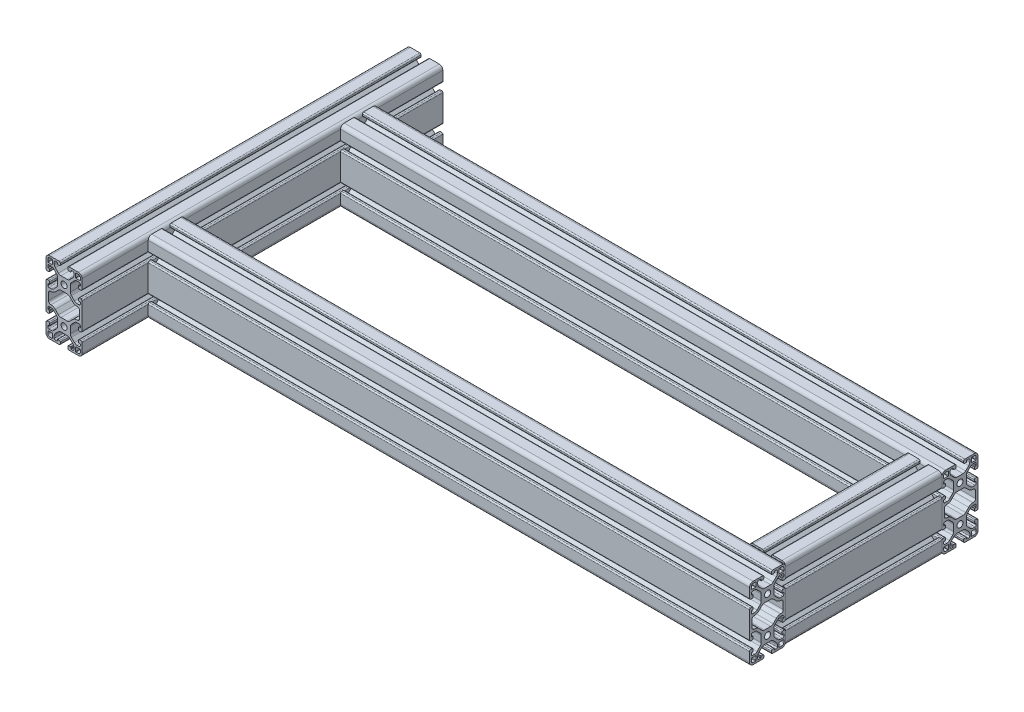
SolidWorks part; units mm, degrees
material "1060 Alloy"
material "1060 Alloy"
material "1060 Alloy"
material "1060 Alloy"
material "1060 Alloy"
ref_plane "Front Plane" through (0, 0, 0) normal (0, 0, 1) x (1, 0, 0)
ref_plane "Top Plane" through (0, 0, 0) normal (0, 1, 0) x (1, 0, 0)
ref_plane "Right Plane" through (0, 0, 0) normal (1, 0, 0) x (0, 0, -1)
sketch3d "3DSketch2"
  line L0 (250, 0, -80) -> (-250, 0, -80)
  line L1 (-265, 0, -150) -> (-265, 0, 150)
  line L2 (-250, 0, -80) -> (-265, 0, -80) construction
  line L3 (0, 0, 80) -> (0, 0, -80) construction
  line L4 (235, 0, -65) -> (235, 0, -80) construction
  line L6 (250, 0, 80) -> (-250, 0, 80)
  line L7 (0, 0, 0) -> (-265, 0, 0) construction
  line L8 (235, 0, 65) -> (235, 0, 80) construction
  line L9 (-250, 0, 80) -> (-265, 0, 80) construction
  line L10 (235, 0, 65) -> (235, 0, -65)
  point P4 (0, 0, 0)
  point P6 (-250, 0, -80)
  point P15 (0, 0, 0)
  point P18 (0, 0, 80)
  dimension "D1" = 15
  dimension "D5" = 160
  dimension "D2" = 300
  dimension "D3" = 15
  dimension "D4" = 500
other "Profile_6 60X30 L(1)" corner treatment butt1
ref_plane "Plane1" through (250, 0, -80) normal (1, 0, 0) x (0, 1, 0)
sketch "Sketch201" plane through (250, 0, -80) normal (1, 0, 0) x (0, 1, 0)
  line L0 (24.95, -13.5) -> (27, -13.5)
  line L1 (24.65, -9.95) -> (24.65, -13.2)
  line L2 (28.2, -9.65) -> (24.95, -9.65)
  line L3 (28.5, -12) -> (28.5, -9.95)
  line L4 (28.5, 9.95) -> (28.5, 12)
  line L5 (24.95, 9.65) -> (28.2, 9.65)
  line L6 (24.65, 13.2) -> (24.65, 9.95)
  line L7 (27, 13.5) -> (24.95, 13.5)
  line L8 (-24.95, 13.5) -> (-27, 13.5)
  line L9 (-24.65, 9.95) -> (-24.65, 13.2)
  line L10 (-28.2, 9.65) -> (-24.95, 9.65)
  line L11 (-28.5, 12) -> (-28.5, 9.95)
  line L12 (-28.5, -9.95) -> (-28.5, -12)
  line L13 (-24.95, -9.65) -> (-28.2, -9.65)
  line L14 (-24.65, -13.2) -> (-24.65, -9.95)
  line L15 (-27, -13.5) -> (-24.95, -13.5)
  line L16 (-4.85, -10.8069) -> (-4.85, -11)
  line L17 (-8.8713, -4.7145) -> (-6.3145, -7.2713)
  line L18 (-9.75, 2.5931) -> (-9.75, -2.5931)
  line L19 (-6.3145, 7.2713) -> (-8.8713, 4.7145)
  line L20 (-4.85, 11) -> (-4.85, 10.8069)
  line L21 (2.85, 13) -> (-2.85, 13)
  line L22 (4.85, 10.8069) -> (4.85, 11)
  line L23 (8.8713, 4.7145) -> (6.3145, 7.2713)
  line L24 (9.75, -2.5931) -> (9.75, 2.5931)
  line L25 (6.3145, -7.2713) -> (8.8713, -4.7145)
  line L26 (4.85, -11) -> (4.85, -10.8069)
  line L27 (-2.85, -13) -> (2.85, -13)
  line L28 (-10.9, -15) -> (10.9, -15)
  line L29 (-11.9, -12.8) -> (-11.9, -14)
  line L30 (-9.7, -12) -> (-11.1, -12)
  line L31 (-9.4, -13.2) -> (-9.4, -12.3)
  line L32 (-7.85, -13.5) -> (-9.1, -13.5)
  line L33 (-6.85, -10.8069) -> (-6.85, -12.5)
  line L34 (-10.2855, -6.1287) -> (-7.7287, -8.6855)
  line L35 (-17.5931, -5.25) -> (-12.4069, -5.25)
  line L36 (-22.2713, -8.6855) -> (-19.7145, -6.1287)
  line L37 (-23.15, -12.5) -> (-23.15, -10.8069)
  line L38 (-20.9, -13.5) -> (-22.15, -13.5)
  line L39 (-20.6, -12.3) -> (-20.6, -13.2)
  line L40 (-18.9, -12) -> (-20.3, -12)
  line L41 (-18.1, -14) -> (-18.1, -12.8)
  line L42 (-27, -15) -> (-19.1, -15)
  line L43 (-30, -4.1) -> (-30, -12)
  line L44 (-27.8, -3.1) -> (-29, -3.1)
  line L45 (-27, -5.3) -> (-27, -3.9)
  line L46 (-28.2, -5.6) -> (-27.3, -5.6)
  line L47 (-28.5, -7.15) -> (-28.5, -5.9)
  line L48 (-25.8069, -8.15) -> (-27.5, -8.15)
  line L49 (-21.1287, -4.7145) -> (-23.6855, -7.2713)
  line L50 (-20.25, 2.5931) -> (-20.25, -2.5931)
  line L51 (-23.6855, 7.2713) -> (-21.1287, 4.7145)
  line L52 (-27.5, 8.15) -> (-25.8069, 8.15)
  line L53 (-28.5, 5.9) -> (-28.5, 7.15)
  line L54 (-27.3, 5.6) -> (-28.2, 5.6)
  line L55 (-27, 3.9) -> (-27, 5.3)
  line L56 (-29, 3.1) -> (-27.8, 3.1)
  line L57 (-30, 12) -> (-30, 4.1)
  line L58 (-19.1, 15) -> (-27, 15)
  line L59 (-18.1, 12.8) -> (-18.1, 14)
  line L60 (-20.3, 12) -> (-18.9, 12)
  line L61 (-20.6, 13.2) -> (-20.6, 12.3)
  line L62 (-22.15, 13.5) -> (-20.9, 13.5)
  line L63 (-23.15, 10.8069) -> (-23.15, 12.5)
  line L64 (-19.7145, 6.1287) -> (-22.2713, 8.6855)
  line L65 (-12.4069, 5.25) -> (-17.5931, 5.25)
  line L66 (-7.7287, 8.6855) -> (-10.2855, 6.1287)
  line L67 (-6.85, 12.5) -> (-6.85, 10.8069)
  line L68 (-9.1, 13.5) -> (-7.85, 13.5)
  line L69 (-9.4, 12.3) -> (-9.4, 13.2)
  line L70 (-11.1, 12) -> (-9.7, 12)
  line L71 (-11.9, 14) -> (-11.9, 12.8)
  line L72 (10.9, 15) -> (-10.9, 15)
  line L73 (11.9, 12.8) -> (11.9, 14)
  line L74 (9.7, 12) -> (11.1, 12)
  line L75 (9.4, 13.2) -> (9.4, 12.3)
  line L76 (7.85, 13.5) -> (9.1, 13.5)
  line L77 (6.85, 10.8069) -> (6.85, 12.5)
  line L78 (10.2855, 6.1287) -> (7.7287, 8.6855)
  line L79 (17.5931, 5.25) -> (12.4069, 5.25)
  line L80 (22.2713, 8.6855) -> (19.7145, 6.1287)
  line L81 (23.15, 12.5) -> (23.15, 10.8069)
  line L82 (20.9, 13.5) -> (22.15, 13.5)
  line L83 (20.6, 12.3) -> (20.6, 13.2)
  line L84 (18.9, 12) -> (20.3, 12)
  line L85 (18.1, 14) -> (18.1, 12.8)
  line L86 (27, 15) -> (19.1, 15)
  line L87 (30, 4.1) -> (30, 12)
  line L88 (27.8, 3.1) -> (29, 3.1)
  line L89 (27, 5.3) -> (27, 3.9)
  line L90 (28.2, 5.6) -> (27.3, 5.6)
  line L91 (28.5, 7.15) -> (28.5, 5.9)
  line L92 (25.8069, 8.15) -> (27.5, 8.15)
  line L93 (21.1287, 4.7145) -> (23.6855, 7.2713)
  line L94 (20.25, -2.5931) -> (20.25, 2.5931)
  line L95 (23.6855, -7.2713) -> (21.1287, -4.7145)
  line L96 (27.5, -8.15) -> (25.8069, -8.15)
  line L97 (28.5, -5.9) -> (28.5, -7.15)
  line L98 (27.3, -5.6) -> (28.2, -5.6)
  line L99 (27, -3.9) -> (27, -5.3)
  line L100 (29, -3.1) -> (27.8, -3.1)
  line L101 (30, -12) -> (30, -4.1)
  line L102 (19.1, -15) -> (27, -15)
  line L103 (18.1, -12.8) -> (18.1, -14)
  line L104 (20.3, -12) -> (18.9, -12)
  line L105 (20.6, -13.2) -> (20.6, -12.3)
  line L106 (22.15, -13.5) -> (20.9, -13.5)
  line L107 (23.15, -10.8069) -> (23.15, -12.5)
  line L108 (19.7145, -6.1287) -> (22.2713, -8.6855)
  line L109 (12.4069, -5.25) -> (17.5931, -5.25)
  line L110 (7.7287, -8.6855) -> (10.2855, -6.1287)
  line L111 (6.85, -12.5) -> (6.85, -10.8069)
  line L112 (9.1, -13.5) -> (7.85, -13.5)
  line L113 (9.4, -12.3) -> (9.4, -13.2)
  line L114 (11.1, -12) -> (9.7, -12)
  line L115 (11.9, -14) -> (11.9, -12.8)
  circle A0 centre (-15, 0) radius 2.5
  circle A1 centre (15, 0) radius 2.5
  arc A2 (24.65, -13.2) -> (24.95, -13.5) centre (24.95, -13.2) ccw
  arc A3 (24.95, -9.65) -> (24.65, -9.95) centre (24.95, -9.95) ccw
  arc A4 (28.5, -9.95) -> (28.2, -9.65) centre (28.2, -9.95) ccw
  arc A5 (27, -13.5) -> (28.5, -12) centre (27, -12) ccw
  arc A6 (28.2, 9.65) -> (28.5, 9.95) centre (28.2, 9.95) ccw
  arc A7 (24.65, 9.95) -> (24.95, 9.65) centre (24.95, 9.95) ccw
  arc A8 (24.95, 13.5) -> (24.65, 13.2) centre (24.95, 13.2) ccw
  arc A9 (28.5, 12) -> (27, 13.5) centre (27, 12) ccw
  arc A10 (-24.65, 13.2) -> (-24.95, 13.5) centre (-24.95, 13.2) ccw
  arc A11 (-24.95, 9.65) -> (-24.65, 9.95) centre (-24.95, 9.95) ccw
  arc A12 (-28.5, 9.95) -> (-28.2, 9.65) centre (-28.2, 9.95) ccw
  arc A13 (-27, 13.5) -> (-28.5, 12) centre (-27, 12) ccw
  arc A14 (-28.2, -9.65) -> (-28.5, -9.95) centre (-28.2, -9.95) ccw
  arc A15 (-24.65, -9.95) -> (-24.95, -9.65) centre (-24.95, -9.95) ccw
  arc A16 (-24.95, -13.5) -> (-24.65, -13.2) centre (-24.95, -13.2) ccw
  arc A17 (-28.5, -12) -> (-27, -13.5) centre (-27, -12) ccw
  arc A18 (-4.85, -11) -> (-2.85, -13) centre (-2.85, -11) ccw
  arc A19 (-4.85, -10.8069) -> (-6.3145, -7.2713) centre (-9.85, -10.8069) ccw
  arc A20 (-9.75, -2.5931) -> (-8.8713, -4.7145) centre (-6.75, -2.5931) ccw
  arc A21 (-8.8713, 4.7145) -> (-9.75, 2.5931) centre (-6.75, 2.5931) ccw
  arc A22 (-6.3145, 7.2713) -> (-4.85, 10.8069) centre (-9.85, 10.8069) ccw
  arc A23 (-2.85, 13) -> (-4.85, 11) centre (-2.85, 11) ccw
  arc A24 (4.85, 11) -> (2.85, 13) centre (2.85, 11) ccw
  arc A25 (4.85, 10.8069) -> (6.3145, 7.2713) centre (9.85, 10.8069) ccw
  arc A26 (9.75, 2.5931) -> (8.8713, 4.7145) centre (6.75, 2.5931) ccw
  arc A27 (8.8713, -4.7145) -> (9.75, -2.5931) centre (6.75, -2.5931) ccw
  arc A28 (6.3145, -7.2713) -> (4.85, -10.8069) centre (9.85, -10.8069) ccw
  arc A29 (2.85, -13) -> (4.85, -11) centre (2.85, -11) ccw
  arc A30 (-11.9, -14) -> (-10.9, -15) centre (-10.9, -14) ccw
  arc A31 (-11.1, -12) -> (-11.9, -12.8) centre (-11.1, -12.8) ccw
  arc A32 (-9.4, -12.3) -> (-9.7, -12) centre (-9.7, -12.3) ccw
  arc A33 (-9.4, -13.2) -> (-9.1, -13.5) centre (-9.1, -13.2) ccw
  arc A34 (-7.85, -13.5) -> (-6.85, -12.5) centre (-7.85, -12.5) ccw
  arc A35 (-6.85, -10.8069) -> (-7.7287, -8.6855) centre (-9.85, -10.8069) ccw
  arc A36 (-10.2855, -6.1287) -> (-12.4069, -5.25) centre (-12.4069, -8.25) ccw
  arc A37 (-17.5931, -5.25) -> (-19.7145, -6.1287) centre (-17.5931, -8.25) ccw
  arc A38 (-22.2713, -8.6855) -> (-23.15, -10.8069) centre (-20.15, -10.8069) ccw
  arc A39 (-23.15, -12.5) -> (-22.15, -13.5) centre (-22.15, -12.5) ccw
  arc A40 (-20.9, -13.5) -> (-20.6, -13.2) centre (-20.9, -13.2) ccw
  arc A41 (-20.3, -12) -> (-20.6, -12.3) centre (-20.3, -12.3) ccw
  arc A42 (-18.1, -12.8) -> (-18.9, -12) centre (-18.9, -12.8) ccw
  arc A43 (-19.1, -15) -> (-18.1, -14) centre (-19.1, -14) ccw
  arc A44 (-30, -12) -> (-27, -15) centre (-27, -12) ccw
  arc A45 (-29, -3.1) -> (-30, -4.1) centre (-29, -4.1) ccw
  arc A46 (-27, -3.9) -> (-27.8, -3.1) centre (-27.8, -3.9) ccw
  arc A47 (-27.3, -5.6) -> (-27, -5.3) centre (-27.3, -5.3) ccw
  arc A48 (-28.2, -5.6) -> (-28.5, -5.9) centre (-28.2, -5.9) ccw
  arc A49 (-28.5, -7.15) -> (-27.5, -8.15) centre (-27.5, -7.15) ccw
  arc A50 (-25.8069, -8.15) -> (-23.6855, -7.2713) centre (-25.8069, -5.15) ccw
  arc A51 (-21.1287, -4.7145) -> (-20.25, -2.5931) centre (-23.25, -2.5931) ccw
  arc A52 (-20.25, 2.5931) -> (-21.1287, 4.7145) centre (-23.25, 2.5931) ccw
  arc A53 (-23.6855, 7.2713) -> (-25.8069, 8.15) centre (-25.8069, 5.15) ccw
  arc A54 (-27.5, 8.15) -> (-28.5, 7.15) centre (-27.5, 7.15) ccw
  arc A55 (-28.5, 5.9) -> (-28.2, 5.6) centre (-28.2, 5.9) ccw
  arc A56 (-27, 5.3) -> (-27.3, 5.6) centre (-27.3, 5.3) ccw
  arc A57 (-27.8, 3.1) -> (-27, 3.9) centre (-27.8, 3.9) ccw
  arc A58 (-30, 4.1) -> (-29, 3.1) centre (-29, 4.1) ccw
  arc A59 (-27, 15) -> (-30, 12) centre (-27, 12) ccw
  arc A60 (-18.1, 14) -> (-19.1, 15) centre (-19.1, 14) ccw
  arc A61 (-18.9, 12) -> (-18.1, 12.8) centre (-18.9, 12.8) ccw
  arc A62 (-20.6, 12.3) -> (-20.3, 12) centre (-20.3, 12.3) ccw
  arc A63 (-20.6, 13.2) -> (-20.9, 13.5) centre (-20.9, 13.2) ccw
  arc A64 (-22.15, 13.5) -> (-23.15, 12.5) centre (-22.15, 12.5) ccw
  arc A65 (-23.15, 10.8069) -> (-22.2713, 8.6855) centre (-20.15, 10.8069) ccw
  arc A66 (-19.7145, 6.1287) -> (-17.5931, 5.25) centre (-17.5931, 8.25) ccw
  arc A67 (-12.4069, 5.25) -> (-10.2855, 6.1287) centre (-12.4069, 8.25) ccw
  arc A68 (-7.7287, 8.6855) -> (-6.85, 10.8069) centre (-9.85, 10.8069) ccw
  arc A69 (-6.85, 12.5) -> (-7.85, 13.5) centre (-7.85, 12.5) ccw
  arc A70 (-9.1, 13.5) -> (-9.4, 13.2) centre (-9.1, 13.2) ccw
  arc A71 (-9.7, 12) -> (-9.4, 12.3) centre (-9.7, 12.3) ccw
  arc A72 (-11.9, 12.8) -> (-11.1, 12) centre (-11.1, 12.8) ccw
  arc A73 (-10.9, 15) -> (-11.9, 14) centre (-10.9, 14) ccw
  arc A74 (11.9, 14) -> (10.9, 15) centre (10.9, 14) ccw
  arc A75 (11.1, 12) -> (11.9, 12.8) centre (11.1, 12.8) ccw
  arc A76 (9.4, 12.3) -> (9.7, 12) centre (9.7, 12.3) ccw
  arc A77 (9.4, 13.2) -> (9.1, 13.5) centre (9.1, 13.2) ccw
  arc A78 (7.85, 13.5) -> (6.85, 12.5) centre (7.85, 12.5) ccw
  arc A79 (6.85, 10.8069) -> (7.7287, 8.6855) centre (9.85, 10.8069) ccw
  arc A80 (10.2855, 6.1287) -> (12.4069, 5.25) centre (12.4069, 8.25) ccw
  arc A81 (17.5931, 5.25) -> (19.7145, 6.1287) centre (17.5931, 8.25) ccw
  arc A82 (22.2713, 8.6855) -> (23.15, 10.8069) centre (20.15, 10.8069) ccw
  arc A83 (23.15, 12.5) -> (22.15, 13.5) centre (22.15, 12.5) ccw
  arc A84 (20.9, 13.5) -> (20.6, 13.2) centre (20.9, 13.2) ccw
  arc A85 (20.3, 12) -> (20.6, 12.3) centre (20.3, 12.3) ccw
  arc A86 (18.1, 12.8) -> (18.9, 12) centre (18.9, 12.8) ccw
  arc A87 (19.1, 15) -> (18.1, 14) centre (19.1, 14) ccw
  arc A88 (30, 12) -> (27, 15) centre (27, 12) ccw
  arc A89 (29, 3.1) -> (30, 4.1) centre (29, 4.1) ccw
  arc A90 (27, 3.9) -> (27.8, 3.1) centre (27.8, 3.9) ccw
  arc A91 (27.3, 5.6) -> (27, 5.3) centre (27.3, 5.3) ccw
  arc A92 (28.2, 5.6) -> (28.5, 5.9) centre (28.2, 5.9) ccw
  arc A93 (28.5, 7.15) -> (27.5, 8.15) centre (27.5, 7.15) ccw
  arc A94 (25.8069, 8.15) -> (23.6855, 7.2713) centre (25.8069, 5.15) ccw
  arc A95 (21.1287, 4.7145) -> (20.25, 2.5931) centre (23.25, 2.5931) ccw
  arc A96 (20.25, -2.5931) -> (21.1287, -4.7145) centre (23.25, -2.5931) ccw
  arc A97 (23.6855, -7.2713) -> (25.8069, -8.15) centre (25.8069, -5.15) ccw
  arc A98 (27.5, -8.15) -> (28.5, -7.15) centre (27.5, -7.15) ccw
  arc A99 (28.5, -5.9) -> (28.2, -5.6) centre (28.2, -5.9) ccw
  arc A100 (27, -5.3) -> (27.3, -5.6) centre (27.3, -5.3) ccw
  arc A101 (27.8, -3.1) -> (27, -3.9) centre (27.8, -3.9) ccw
  arc A102 (30, -4.1) -> (29, -3.1) centre (29, -4.1) ccw
  arc A103 (27, -15) -> (30, -12) centre (27, -12) ccw
  arc A104 (18.1, -14) -> (19.1, -15) centre (19.1, -14) ccw
  arc A105 (18.9, -12) -> (18.1, -12.8) centre (18.9, -12.8) ccw
  arc A106 (20.6, -12.3) -> (20.3, -12) centre (20.3, -12.3) ccw
  arc A107 (20.6, -13.2) -> (20.9, -13.5) centre (20.9, -13.2) ccw
  arc A108 (22.15, -13.5) -> (23.15, -12.5) centre (22.15, -12.5) ccw
  arc A109 (23.15, -10.8069) -> (22.2713, -8.6855) centre (20.15, -10.8069) ccw
  arc A110 (19.7145, -6.1287) -> (17.5931, -5.25) centre (17.5931, -8.25) ccw
  arc A111 (12.4069, -5.25) -> (10.2855, -6.1287) centre (12.4069, -8.25) ccw
  arc A112 (7.7287, -8.6855) -> (6.85, -10.8069) centre (9.85, -10.8069) ccw
  arc A113 (6.85, -12.5) -> (7.85, -13.5) centre (7.85, -12.5) ccw
  arc A114 (9.1, -13.5) -> (9.4, -13.2) centre (9.1, -13.2) ccw
  arc A115 (9.7, -12) -> (9.4, -12.3) centre (9.7, -12.3) ccw
  arc A116 (11.9, -12.8) -> (11.1, -12) centre (11.1, -12.8) ccw
  arc A117 (10.9, -15) -> (11.9, -14) centre (10.9, -14) ccw
  point P344 (0, 0)
other "Profile_6 60X30 L(2)" corner treatment butt1
ref_plane "Plane2" through (235, 0, 65) normal (0, 0, -1) x (0, 1, 0)
sketch "Sketch202" plane through (235, 0, 65) normal (0, 0, -1) x (0, 1, 0)
  line L0 (24.95, -13.5) -> (27, -13.5)
  line L1 (24.65, -9.95) -> (24.65, -13.2)
  line L2 (28.2, -9.65) -> (24.95, -9.65)
  line L3 (28.5, -12) -> (28.5, -9.95)
  line L4 (28.5, 9.95) -> (28.5, 12)
  line L5 (24.95, 9.65) -> (28.2, 9.65)
  line L6 (24.65, 13.2) -> (24.65, 9.95)
  line L7 (27, 13.5) -> (24.95, 13.5)
  line L8 (-24.95, 13.5) -> (-27, 13.5)
  line L9 (-24.65, 9.95) -> (-24.65, 13.2)
  line L10 (-28.2, 9.65) -> (-24.95, 9.65)
  line L11 (-28.5, 12) -> (-28.5, 9.95)
  line L12 (-28.5, -9.95) -> (-28.5, -12)
  line L13 (-24.95, -9.65) -> (-28.2, -9.65)
  line L14 (-24.65, -13.2) -> (-24.65, -9.95)
  line L15 (-27, -13.5) -> (-24.95, -13.5)
  line L16 (-4.85, -10.8069) -> (-4.85, -11)
  line L17 (-8.8713, -4.7145) -> (-6.3145, -7.2713)
  line L18 (-9.75, 2.5931) -> (-9.75, -2.5931)
  line L19 (-6.3145, 7.2713) -> (-8.8713, 4.7145)
  line L20 (-4.85, 11) -> (-4.85, 10.8069)
  line L21 (2.85, 13) -> (-2.85, 13)
  line L22 (4.85, 10.8069) -> (4.85, 11)
  line L23 (8.8713, 4.7145) -> (6.3145, 7.2713)
  line L24 (9.75, -2.5931) -> (9.75, 2.5931)
  line L25 (6.3145, -7.2713) -> (8.8713, -4.7145)
  line L26 (4.85, -11) -> (4.85, -10.8069)
  line L27 (-2.85, -13) -> (2.85, -13)
  line L28 (-10.9, -15) -> (10.9, -15)
  line L29 (-11.9, -12.8) -> (-11.9, -14)
  line L30 (-9.7, -12) -> (-11.1, -12)
  line L31 (-9.4, -13.2) -> (-9.4, -12.3)
  line L32 (-7.85, -13.5) -> (-9.1, -13.5)
  line L33 (-6.85, -10.8069) -> (-6.85, -12.5)
  line L34 (-10.2855, -6.1287) -> (-7.7287, -8.6855)
  line L35 (-17.5931, -5.25) -> (-12.4069, -5.25)
  line L36 (-22.2713, -8.6855) -> (-19.7145, -6.1287)
  line L37 (-23.15, -12.5) -> (-23.15, -10.8069)
  line L38 (-20.9, -13.5) -> (-22.15, -13.5)
  line L39 (-20.6, -12.3) -> (-20.6, -13.2)
  line L40 (-18.9, -12) -> (-20.3, -12)
  line L41 (-18.1, -14) -> (-18.1, -12.8)
  line L42 (-27, -15) -> (-19.1, -15)
  line L43 (-30, -4.1) -> (-30, -12)
  line L44 (-27.8, -3.1) -> (-29, -3.1)
  line L45 (-27, -5.3) -> (-27, -3.9)
  line L46 (-28.2, -5.6) -> (-27.3, -5.6)
  line L47 (-28.5, -7.15) -> (-28.5, -5.9)
  line L48 (-25.8069, -8.15) -> (-27.5, -8.15)
  line L49 (-21.1287, -4.7145) -> (-23.6855, -7.2713)
  line L50 (-20.25, 2.5931) -> (-20.25, -2.5931)
  line L51 (-23.6855, 7.2713) -> (-21.1287, 4.7145)
  line L52 (-27.5, 8.15) -> (-25.8069, 8.15)
  line L53 (-28.5, 5.9) -> (-28.5, 7.15)
  line L54 (-27.3, 5.6) -> (-28.2, 5.6)
  line L55 (-27, 3.9) -> (-27, 5.3)
  line L56 (-29, 3.1) -> (-27.8, 3.1)
  line L57 (-30, 12) -> (-30, 4.1)
  line L58 (-19.1, 15) -> (-27, 15)
  line L59 (-18.1, 12.8) -> (-18.1, 14)
  line L60 (-20.3, 12) -> (-18.9, 12)
  line L61 (-20.6, 13.2) -> (-20.6, 12.3)
  line L62 (-22.15, 13.5) -> (-20.9, 13.5)
  line L63 (-23.15, 10.8069) -> (-23.15, 12.5)
  line L64 (-19.7145, 6.1287) -> (-22.2713, 8.6855)
  line L65 (-12.4069, 5.25) -> (-17.5931, 5.25)
  line L66 (-7.7287, 8.6855) -> (-10.2855, 6.1287)
  line L67 (-6.85, 12.5) -> (-6.85, 10.8069)
  line L68 (-9.1, 13.5) -> (-7.85, 13.5)
  line L69 (-9.4, 12.3) -> (-9.4, 13.2)
  line L70 (-11.1, 12) -> (-9.7, 12)
  line L71 (-11.9, 14) -> (-11.9, 12.8)
  line L72 (10.9, 15) -> (-10.9, 15)
  line L73 (11.9, 12.8) -> (11.9, 14)
  line L74 (9.7, 12) -> (11.1, 12)
  line L75 (9.4, 13.2) -> (9.4, 12.3)
  line L76 (7.85, 13.5) -> (9.1, 13.5)
  line L77 (6.85, 10.8069) -> (6.85, 12.5)
  line L78 (10.2855, 6.1287) -> (7.7287, 8.6855)
  line L79 (17.5931, 5.25) -> (12.4069, 5.25)
  line L80 (22.2713, 8.6855) -> (19.7145, 6.1287)
  line L81 (23.15, 12.5) -> (23.15, 10.8069)
  line L82 (20.9, 13.5) -> (22.15, 13.5)
  line L83 (20.6, 12.3) -> (20.6, 13.2)
  line L84 (18.9, 12) -> (20.3, 12)
  line L85 (18.1, 14) -> (18.1, 12.8)
  line L86 (27, 15) -> (19.1, 15)
  line L87 (30, 4.1) -> (30, 12)
  line L88 (27.8, 3.1) -> (29, 3.1)
  line L89 (27, 5.3) -> (27, 3.9)
  line L90 (28.2, 5.6) -> (27.3, 5.6)
  line L91 (28.5, 7.15) -> (28.5, 5.9)
  line L92 (25.8069, 8.15) -> (27.5, 8.15)
  line L93 (21.1287, 4.7145) -> (23.6855, 7.2713)
  line L94 (20.25, -2.5931) -> (20.25, 2.5931)
  line L95 (23.6855, -7.2713) -> (21.1287, -4.7145)
  line L96 (27.5, -8.15) -> (25.8069, -8.15)
  line L97 (28.5, -5.9) -> (28.5, -7.15)
  line L98 (27.3, -5.6) -> (28.2, -5.6)
  line L99 (27, -3.9) -> (27, -5.3)
  line L100 (29, -3.1) -> (27.8, -3.1)
  line L101 (30, -12) -> (30, -4.1)
  line L102 (19.1, -15) -> (27, -15)
  line L103 (18.1, -12.8) -> (18.1, -14)
  line L104 (20.3, -12) -> (18.9, -12)
  line L105 (20.6, -13.2) -> (20.6, -12.3)
  line L106 (22.15, -13.5) -> (20.9, -13.5)
  line L107 (23.15, -10.8069) -> (23.15, -12.5)
  line L108 (19.7145, -6.1287) -> (22.2713, -8.6855)
  line L109 (12.4069, -5.25) -> (17.5931, -5.25)
  line L110 (7.7287, -8.6855) -> (10.2855, -6.1287)
  line L111 (6.85, -12.5) -> (6.85, -10.8069)
  line L112 (9.1, -13.5) -> (7.85, -13.5)
  line L113 (9.4, -12.3) -> (9.4, -13.2)
  line L114 (11.1, -12) -> (9.7, -12)
  line L115 (11.9, -14) -> (11.9, -12.8)
  circle A0 centre (-15, 0) radius 2.5
  circle A1 centre (15, 0) radius 2.5
  arc A2 (24.65, -13.2) -> (24.95, -13.5) centre (24.95, -13.2) ccw
  arc A3 (24.95, -9.65) -> (24.65, -9.95) centre (24.95, -9.95) ccw
  arc A4 (28.5, -9.95) -> (28.2, -9.65) centre (28.2, -9.95) ccw
  arc A5 (27, -13.5) -> (28.5, -12) centre (27, -12) ccw
  arc A6 (28.2, 9.65) -> (28.5, 9.95) centre (28.2, 9.95) ccw
  arc A7 (24.65, 9.95) -> (24.95, 9.65) centre (24.95, 9.95) ccw
  arc A8 (24.95, 13.5) -> (24.65, 13.2) centre (24.95, 13.2) ccw
  arc A9 (28.5, 12) -> (27, 13.5) centre (27, 12) ccw
  arc A10 (-24.65, 13.2) -> (-24.95, 13.5) centre (-24.95, 13.2) ccw
  arc A11 (-24.95, 9.65) -> (-24.65, 9.95) centre (-24.95, 9.95) ccw
  arc A12 (-28.5, 9.95) -> (-28.2, 9.65) centre (-28.2, 9.95) ccw
  arc A13 (-27, 13.5) -> (-28.5, 12) centre (-27, 12) ccw
  arc A14 (-28.2, -9.65) -> (-28.5, -9.95) centre (-28.2, -9.95) ccw
  arc A15 (-24.65, -9.95) -> (-24.95, -9.65) centre (-24.95, -9.95) ccw
  arc A16 (-24.95, -13.5) -> (-24.65, -13.2) centre (-24.95, -13.2) ccw
  arc A17 (-28.5, -12) -> (-27, -13.5) centre (-27, -12) ccw
  arc A18 (-4.85, -11) -> (-2.85, -13) centre (-2.85, -11) ccw
  arc A19 (-4.85, -10.8069) -> (-6.3145, -7.2713) centre (-9.85, -10.8069) ccw
  arc A20 (-9.75, -2.5931) -> (-8.8713, -4.7145) centre (-6.75, -2.5931) ccw
  arc A21 (-8.8713, 4.7145) -> (-9.75, 2.5931) centre (-6.75, 2.5931) ccw
  arc A22 (-6.3145, 7.2713) -> (-4.85, 10.8069) centre (-9.85, 10.8069) ccw
  arc A23 (-2.85, 13) -> (-4.85, 11) centre (-2.85, 11) ccw
  arc A24 (4.85, 11) -> (2.85, 13) centre (2.85, 11) ccw
  arc A25 (4.85, 10.8069) -> (6.3145, 7.2713) centre (9.85, 10.8069) ccw
  arc A26 (9.75, 2.5931) -> (8.8713, 4.7145) centre (6.75, 2.5931) ccw
  arc A27 (8.8713, -4.7145) -> (9.75, -2.5931) centre (6.75, -2.5931) ccw
  arc A28 (6.3145, -7.2713) -> (4.85, -10.8069) centre (9.85, -10.8069) ccw
  arc A29 (2.85, -13) -> (4.85, -11) centre (2.85, -11) ccw
  arc A30 (-11.9, -14) -> (-10.9, -15) centre (-10.9, -14) ccw
  arc A31 (-11.1, -12) -> (-11.9, -12.8) centre (-11.1, -12.8) ccw
  arc A32 (-9.4, -12.3) -> (-9.7, -12) centre (-9.7, -12.3) ccw
  arc A33 (-9.4, -13.2) -> (-9.1, -13.5) centre (-9.1, -13.2) ccw
  arc A34 (-7.85, -13.5) -> (-6.85, -12.5) centre (-7.85, -12.5) ccw
  arc A35 (-6.85, -10.8069) -> (-7.7287, -8.6855) centre (-9.85, -10.8069) ccw
  arc A36 (-10.2855, -6.1287) -> (-12.4069, -5.25) centre (-12.4069, -8.25) ccw
  arc A37 (-17.5931, -5.25) -> (-19.7145, -6.1287) centre (-17.5931, -8.25) ccw
  arc A38 (-22.2713, -8.6855) -> (-23.15, -10.8069) centre (-20.15, -10.8069) ccw
  arc A39 (-23.15, -12.5) -> (-22.15, -13.5) centre (-22.15, -12.5) ccw
  arc A40 (-20.9, -13.5) -> (-20.6, -13.2) centre (-20.9, -13.2) ccw
  arc A41 (-20.3, -12) -> (-20.6, -12.3) centre (-20.3, -12.3) ccw
  arc A42 (-18.1, -12.8) -> (-18.9, -12) centre (-18.9, -12.8) ccw
  arc A43 (-19.1, -15) -> (-18.1, -14) centre (-19.1, -14) ccw
  arc A44 (-30, -12) -> (-27, -15) centre (-27, -12) ccw
  arc A45 (-29, -3.1) -> (-30, -4.1) centre (-29, -4.1) ccw
  arc A46 (-27, -3.9) -> (-27.8, -3.1) centre (-27.8, -3.9) ccw
  arc A47 (-27.3, -5.6) -> (-27, -5.3) centre (-27.3, -5.3) ccw
  arc A48 (-28.2, -5.6) -> (-28.5, -5.9) centre (-28.2, -5.9) ccw
  arc A49 (-28.5, -7.15) -> (-27.5, -8.15) centre (-27.5, -7.15) ccw
  arc A50 (-25.8069, -8.15) -> (-23.6855, -7.2713) centre (-25.8069, -5.15) ccw
  arc A51 (-21.1287, -4.7145) -> (-20.25, -2.5931) centre (-23.25, -2.5931) ccw
  arc A52 (-20.25, 2.5931) -> (-21.1287, 4.7145) centre (-23.25, 2.5931) ccw
  arc A53 (-23.6855, 7.2713) -> (-25.8069, 8.15) centre (-25.8069, 5.15) ccw
  arc A54 (-27.5, 8.15) -> (-28.5, 7.15) centre (-27.5, 7.15) ccw
  arc A55 (-28.5, 5.9) -> (-28.2, 5.6) centre (-28.2, 5.9) ccw
  arc A56 (-27, 5.3) -> (-27.3, 5.6) centre (-27.3, 5.3) ccw
  arc A57 (-27.8, 3.1) -> (-27, 3.9) centre (-27.8, 3.9) ccw
  arc A58 (-30, 4.1) -> (-29, 3.1) centre (-29, 4.1) ccw
  arc A59 (-27, 15) -> (-30, 12) centre (-27, 12) ccw
  arc A60 (-18.1, 14) -> (-19.1, 15) centre (-19.1, 14) ccw
  arc A61 (-18.9, 12) -> (-18.1, 12.8) centre (-18.9, 12.8) ccw
  arc A62 (-20.6, 12.3) -> (-20.3, 12) centre (-20.3, 12.3) ccw
  arc A63 (-20.6, 13.2) -> (-20.9, 13.5) centre (-20.9, 13.2) ccw
  arc A64 (-22.15, 13.5) -> (-23.15, 12.5) centre (-22.15, 12.5) ccw
  arc A65 (-23.15, 10.8069) -> (-22.2713, 8.6855) centre (-20.15, 10.8069) ccw
  arc A66 (-19.7145, 6.1287) -> (-17.5931, 5.25) centre (-17.5931, 8.25) ccw
  arc A67 (-12.4069, 5.25) -> (-10.2855, 6.1287) centre (-12.4069, 8.25) ccw
  arc A68 (-7.7287, 8.6855) -> (-6.85, 10.8069) centre (-9.85, 10.8069) ccw
  arc A69 (-6.85, 12.5) -> (-7.85, 13.5) centre (-7.85, 12.5) ccw
  arc A70 (-9.1, 13.5) -> (-9.4, 13.2) centre (-9.1, 13.2) ccw
  arc A71 (-9.7, 12) -> (-9.4, 12.3) centre (-9.7, 12.3) ccw
  arc A72 (-11.9, 12.8) -> (-11.1, 12) centre (-11.1, 12.8) ccw
  arc A73 (-10.9, 15) -> (-11.9, 14) centre (-10.9, 14) ccw
  arc A74 (11.9, 14) -> (10.9, 15) centre (10.9, 14) ccw
  arc A75 (11.1, 12) -> (11.9, 12.8) centre (11.1, 12.8) ccw
  arc A76 (9.4, 12.3) -> (9.7, 12) centre (9.7, 12.3) ccw
  arc A77 (9.4, 13.2) -> (9.1, 13.5) centre (9.1, 13.2) ccw
  arc A78 (7.85, 13.5) -> (6.85, 12.5) centre (7.85, 12.5) ccw
  arc A79 (6.85, 10.8069) -> (7.7287, 8.6855) centre (9.85, 10.8069) ccw
  arc A80 (10.2855, 6.1287) -> (12.4069, 5.25) centre (12.4069, 8.25) ccw
  arc A81 (17.5931, 5.25) -> (19.7145, 6.1287) centre (17.5931, 8.25) ccw
  arc A82 (22.2713, 8.6855) -> (23.15, 10.8069) centre (20.15, 10.8069) ccw
  arc A83 (23.15, 12.5) -> (22.15, 13.5) centre (22.15, 12.5) ccw
  arc A84 (20.9, 13.5) -> (20.6, 13.2) centre (20.9, 13.2) ccw
  arc A85 (20.3, 12) -> (20.6, 12.3) centre (20.3, 12.3) ccw
  arc A86 (18.1, 12.8) -> (18.9, 12) centre (18.9, 12.8) ccw
  arc A87 (19.1, 15) -> (18.1, 14) centre (19.1, 14) ccw
  arc A88 (30, 12) -> (27, 15) centre (27, 12) ccw
  arc A89 (29, 3.1) -> (30, 4.1) centre (29, 4.1) ccw
  arc A90 (27, 3.9) -> (27.8, 3.1) centre (27.8, 3.9) ccw
  arc A91 (27.3, 5.6) -> (27, 5.3) centre (27.3, 5.3) ccw
  arc A92 (28.2, 5.6) -> (28.5, 5.9) centre (28.2, 5.9) ccw
  arc A93 (28.5, 7.15) -> (27.5, 8.15) centre (27.5, 7.15) ccw
  arc A94 (25.8069, 8.15) -> (23.6855, 7.2713) centre (25.8069, 5.15) ccw
  arc A95 (21.1287, 4.7145) -> (20.25, 2.5931) centre (23.25, 2.5931) ccw
  arc A96 (20.25, -2.5931) -> (21.1287, -4.7145) centre (23.25, -2.5931) ccw
  arc A97 (23.6855, -7.2713) -> (25.8069, -8.15) centre (25.8069, -5.15) ccw
  arc A98 (27.5, -8.15) -> (28.5, -7.15) centre (27.5, -7.15) ccw
  arc A99 (28.5, -5.9) -> (28.2, -5.6) centre (28.2, -5.9) ccw
  arc A100 (27, -5.3) -> (27.3, -5.6) centre (27.3, -5.3) ccw
  arc A101 (27.8, -3.1) -> (27, -3.9) centre (27.8, -3.9) ccw
  arc A102 (30, -4.1) -> (29, -3.1) centre (29, -4.1) ccw
  arc A103 (27, -15) -> (30, -12) centre (27, -12) ccw
  arc A104 (18.1, -14) -> (19.1, -15) centre (19.1, -14) ccw
  arc A105 (18.9, -12) -> (18.1, -12.8) centre (18.9, -12.8) ccw
  arc A106 (20.6, -12.3) -> (20.3, -12) centre (20.3, -12.3) ccw
  arc A107 (20.6, -13.2) -> (20.9, -13.5) centre (20.9, -13.2) ccw
  arc A108 (22.15, -13.5) -> (23.15, -12.5) centre (22.15, -12.5) ccw
  arc A109 (23.15, -10.8069) -> (22.2713, -8.6855) centre (20.15, -10.8069) ccw
  arc A110 (19.7145, -6.1287) -> (17.5931, -5.25) centre (17.5931, -8.25) ccw
  arc A111 (12.4069, -5.25) -> (10.2855, -6.1287) centre (12.4069, -8.25) ccw
  arc A112 (7.7287, -8.6855) -> (6.85, -10.8069) centre (9.85, -10.8069) ccw
  arc A113 (6.85, -12.5) -> (7.85, -13.5) centre (7.85, -12.5) ccw
  arc A114 (9.1, -13.5) -> (9.4, -13.2) centre (9.1, -13.2) ccw
  arc A115 (9.7, -12) -> (9.4, -12.3) centre (9.7, -12.3) ccw
  arc A116 (11.9, -12.8) -> (11.1, -12) centre (11.1, -12.8) ccw
  arc A117 (10.9, -15) -> (11.9, -14) centre (10.9, -14) ccw
  point P344 (0, 0)
hole_wizard "Ø5.5 (5.5) Diameter Hole2" positions "Sketch14" profile "Sketch15" hole size "Ø5.5" standard "ISO" end condition through all
sketch "Sketch14" plane through (0, 0, 95) normal (0, 0, 1) x (1, 0, 0)
  point P0 (235, -15)
  point P3 (235, 15)
sketch "Sketch15" plane through (235, -15, 95) normal (1, 0, 0) x (0, -1, 0)
  line L0 (0, 0) -> (0, 245)
  line L1 (0, 245) -> (2.75, 245)
  line L2 (2.75, 245) -> (2.75, 0)
  line L5 (2.75, 0) -> (0, 0)
  line L11 (0, -6.35) -> (0, 107.95) construction
  dimension "Thru Hole Dia." = 5.5
  dimension "Thru Hole Depth" = 245
hole_wizard "Ø5.5 (5.5) Diameter Hole3" positions "Sketch18" profile "Sketch17" hole size "Ø5.5" standard "ISO" end condition through all
sketch "Sketch18" plane through (-280, 0, 0) normal (-1, 0, 0) x (0, 0, 1)
  point P0 (80, -15)
  point P3 (80, 15)
  point P6 (-80, 15)
  point P9 (-80, -15)
sketch "Sketch17" plane through (-280, -15, 80) normal (0, 1, 0) x (0, 0, 1)
  line L0 (0, 0) -> (0, 530)
  line L1 (0, 530) -> (2.75, 530)
  line L2 (2.75, 530) -> (2.75, 0)
  line L5 (2.75, 0) -> (0, 0)
  line L11 (0, -6.35) -> (0, 107.95) construction
  dimension "Thru Hole Dia." = 5.5
  dimension "Thru Hole Depth" = 530
hole_wizard "M6 Tapped Hole1" positions "Sketch19" profile "Sketch20" tap size "M6" standard "ISO"
sketch "Sketch19" plane through (0, 0, -65) normal (0, 0, -1) x (-1, 0, 0)
  point P0 (-235, -15)
  point P3 (-235, 15)
sketch "Sketch20" plane through (235, -15, -65) normal (1, 0, 0) x (0, 1, 0)
  line L0 (0, 0) -> (0, 18.5142)
  line L1 (0, 18.5142) -> (2.52, 17)
  line L2 (2.52, 17) -> (2.52, 0)
  line L5 (2.52, 0) -> (0, 0)
  line L10 (0, 18.5142) -> (-2.52, 17) construction
  line L11 (0, -6.35) -> (0, 107.95) construction
  dimension "Tap Drill Dia." = 5.04
  dimension "Tap Drill Depth" = 17
  dimension "Drill Angle" = 118
cosmetic thread "Hole Thread1"
cosmetic thread "Hole Thread2"
hole_wizard "M6 Tapped Hole2" positions "Sketch21" profile "Sketch22" tap size "M6" standard "ISO"
sketch "Sketch21" plane through (-250, 0, 0) normal (-1, 0, 0) x (0, 0, 1)
  point P0 (-80, 15)
  point P3 (-80, -15)
  point P17 (80, -15)
  point P20 (80, 15)
sketch "Sketch22" plane through (-250, 15, -80) normal (0, 1, 0) x (0, 0, 1)
  line L0 (0, 0) -> (0, 18.5142)
  line L1 (0, 18.5142) -> (2.52, 17)
  line L2 (2.52, 17) -> (2.52, 0)
  line L5 (2.52, 0) -> (0, 0)
  line L10 (0, 18.5142) -> (-2.52, 17) construction
  line L11 (0, -6.35) -> (0, 107.95) construction
  dimension "Tap Drill Dia." = 5.04
  dimension "Tap Drill Depth" = 17
  dimension "Drill Angle" = 118
cosmetic thread "Hole Thread3"
cosmetic thread "Hole Thread4"
cosmetic thread "Hole Thread5"
cosmetic thread "Hole Thread6"
hole_wizard "M6 Tapped Hole11" positions "Sketch25" profile "Sketch26" tap size "M6" standard "ISO"
sketch "Sketch25" plane through (0, 0, 65) normal (0, 0, 1) x (1, 0, 0)
  point P0 (235, -15)
  point P3 (235, 15)
sketch "Sketch26" plane through (235, -15, 65) normal (1, 0, 0) x (0, -1, 0)
  line L0 (0, 0) -> (0, 18.5142)
  line L1 (0, 18.5142) -> (2.52, 17)
  line L2 (2.52, 17) -> (2.52, 0)
  line L5 (2.52, 0) -> (0, 0)
  line L10 (0, 18.5142) -> (-2.52, 17) construction
  line L11 (0, -6.35) -> (0, 107.95) construction
  dimension "Tap Drill Dia." = 5.04
  dimension "Tap Drill Depth" = 17
  dimension "Drill Angle" = 118
cosmetic thread "Hole Thread7"
cosmetic thread "Hole Thread8"
hole_wizard "M6 Tapped Hole12" positions "Sketch203" profile "Sketch204" tap size "M6" standard "ISO"
sketch "Sketch203" plane through (0, 0, 150) normal (0, 0, 1) x (1, 0, 0)
  point P0 (-265, 15)
  point P3 (-265, -15)
sketch "Sketch204" plane through (-265, 15, 150) normal (1, 0, 0) x (0, -1, 0)
  line L0 (0, 0) -> (0, 18.5142)
  line L1 (0, 18.5142) -> (2.52, 17)
  line L2 (2.52, 17) -> (2.52, 0)
  line L5 (2.52, 0) -> (0, 0)
  line L10 (0, 18.5142) -> (-2.52, 17) construction
  line L11 (0, -6.35) -> (0, 107.95) construction
  dimension "Tap Drill Dia." = 5.04
  dimension "Tap Drill Depth" = 17
  dimension "Drill Angle" = 118
cosmetic thread "Hole Thread9"
cosmetic thread "Hole Thread10"
hole_wizard "M6 Tapped Hole13" positions "Sketch205" profile "Sketch206" tap size "M6" standard "ISO"
sketch "Sketch205" plane through (0, 0, -150) normal (0, 0, -1) x (-1, 0, 0)
  point P0 (265, 15)
  point P3 (265, -15)
sketch "Sketch206" plane through (-265, 15, -150) normal (1, 0, 0) x (0, 1, 0)
  line L0 (0, 0) -> (0, 18.5142)
  line L1 (0, 18.5142) -> (2.52, 17)
  line L2 (2.52, 17) -> (2.52, 0)
  line L5 (2.52, 0) -> (0, 0)
  line L10 (0, 18.5142) -> (-2.52, 17) construction
  line L11 (0, -6.35) -> (0, 107.95) construction
  dimension "Tap Drill Dia." = 5.04
  dimension "Tap Drill Depth" = 17
  dimension "Drill Angle" = 118
cosmetic thread "Hole Thread11"
cosmetic thread "Hole Thread12"
